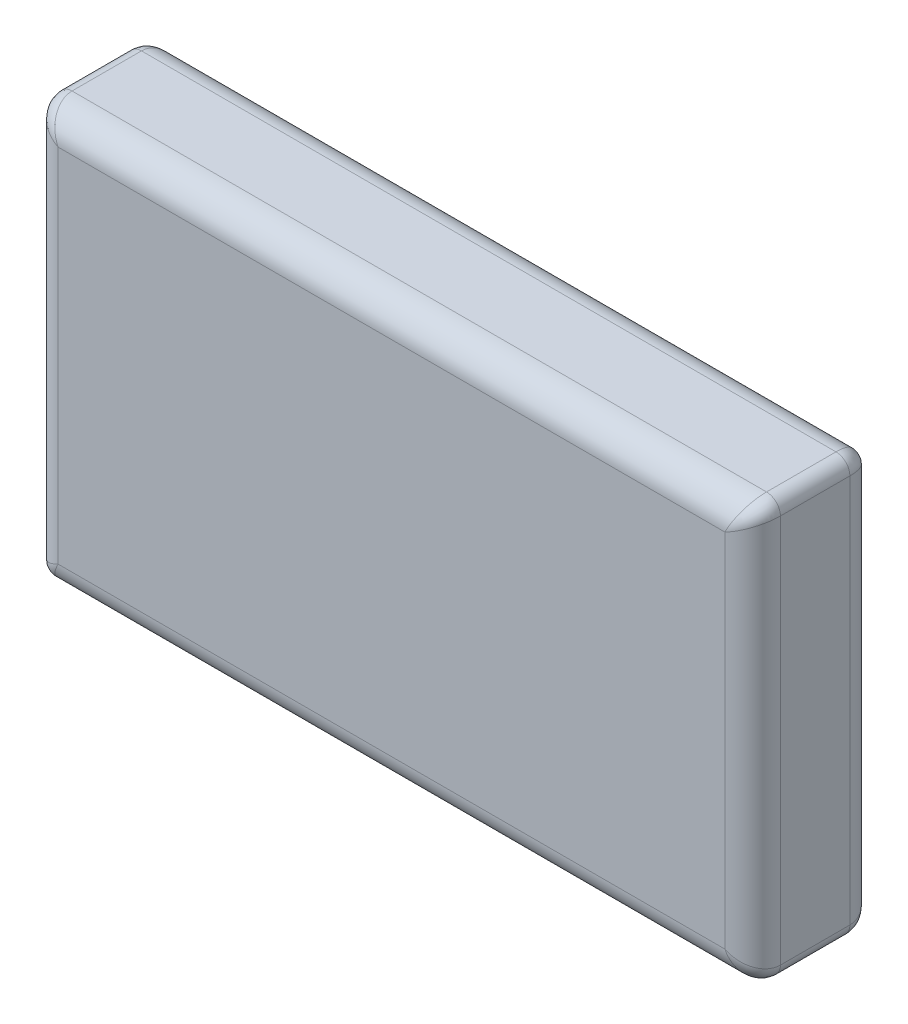
SolidWorks part; units mm, degrees
ref_plane "Plan de face" through (0, 0, 0) normal (0, 0, 1) x (1, 0, 0)
ref_plane "Plan de dessus" through (0, 0, 0) normal (0, 1, 0) x (1, 0, 0)
ref_plane "Plan de droite" through (0, 0, 0) normal (1, 0, 0) x (0, 0, -1)
sketch "Esquisse1" plane through (0, 0, 0) normal (0, 0, 1) x (1, 0, 0)
  line L1 (-25, -15) -> (25, -15)
  line L2 (-26, -14) -> (-26, 14)
  line L3 (-25, 15) -> (25, 15)
  line L4 (26, -14) -> (26, 14)
  line L5 (-26, -15) -> (26, 15) construction
  line L6 (-26, 15) -> (26, -15) construction
  arc A0 (-25, -15) -> (-26, -14) centre (-25, -14) cw
  arc A1 (25, -15) -> (26, -14) centre (25, -14) ccw
  arc A2 (25, 15) -> (26, 14) centre (25, 14) cw
  arc A3 (-26, 14) -> (-25, 15) centre (-25, 14) cw
  point P0 (0, 0)
  dimension "D3" = 1
  dimension "D1" = 52
  dimension "D2" = 30
extrude "Boss.-Extru.1" add sketch "Esquisse1" along normal blind 9
fillet "Congé1" radius 2 16 edges at (0, -15, 0) (25.7071, -14.7071, 0) (26, 0, 0) (25.7071, 14.7071, 0) (0, 15, 0) (-25.7071, 14.7071, 0) (-26, 0, 0) (-25.7071, -14.7071, 0) (-26, 0, 9) (-25.7071, 14.7071, 9) (0, 15, 9) (25.7071, 14.7071, 9) (26, 0, 9) (25.7071, -14.7071, 9) (0, -15, 9) (-25.7071, -14.7071, 9)
